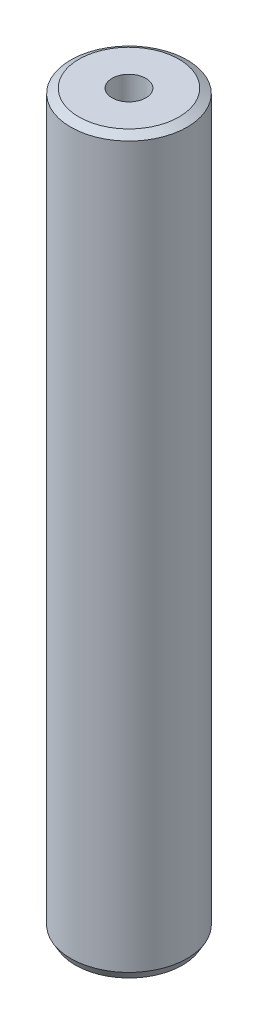
SolidWorks part; units mm, degrees
ref_plane "Front Plane" through (0, 0, 0) normal (0, 0, 1) x (1, 0, 0)
ref_plane "Top Plane" through (0, 0, 0) normal (0, 1, 0) x (1, 0, 0)
ref_plane "Right Plane" through (0, 0, 0) normal (1, 0, 0) x (0, 0, -1)
sketch "Sketch1" plane through (0, 0, 0) normal (0, 1, 0) x (1, 0, 0)
  circle A0 centre (0, 0) radius 35
  dimension "SHAFT_OD" = 70
extrude "Boss-Extrude1" add sketch "Sketch1" along normal blind 440.4805
sketch "Sketch2" plane through (0, 0, 0) normal (0, 1, 0) x (1, 0, 0)
  circle A0 centre (0, 0) radius 10.1756
  dimension "BORE_D" = 20.3512
extrude "Cut-Extrude1" cut sketch "Sketch2" along normal through all
chamfer "Chamfer1" distance 2.8378 angle 60 2 edges at (0, 440.4805, 35) (0, 0, 35) first distance on face at (0, 440.4805, 35) first distance on face at (0, 0, 10.1756)
